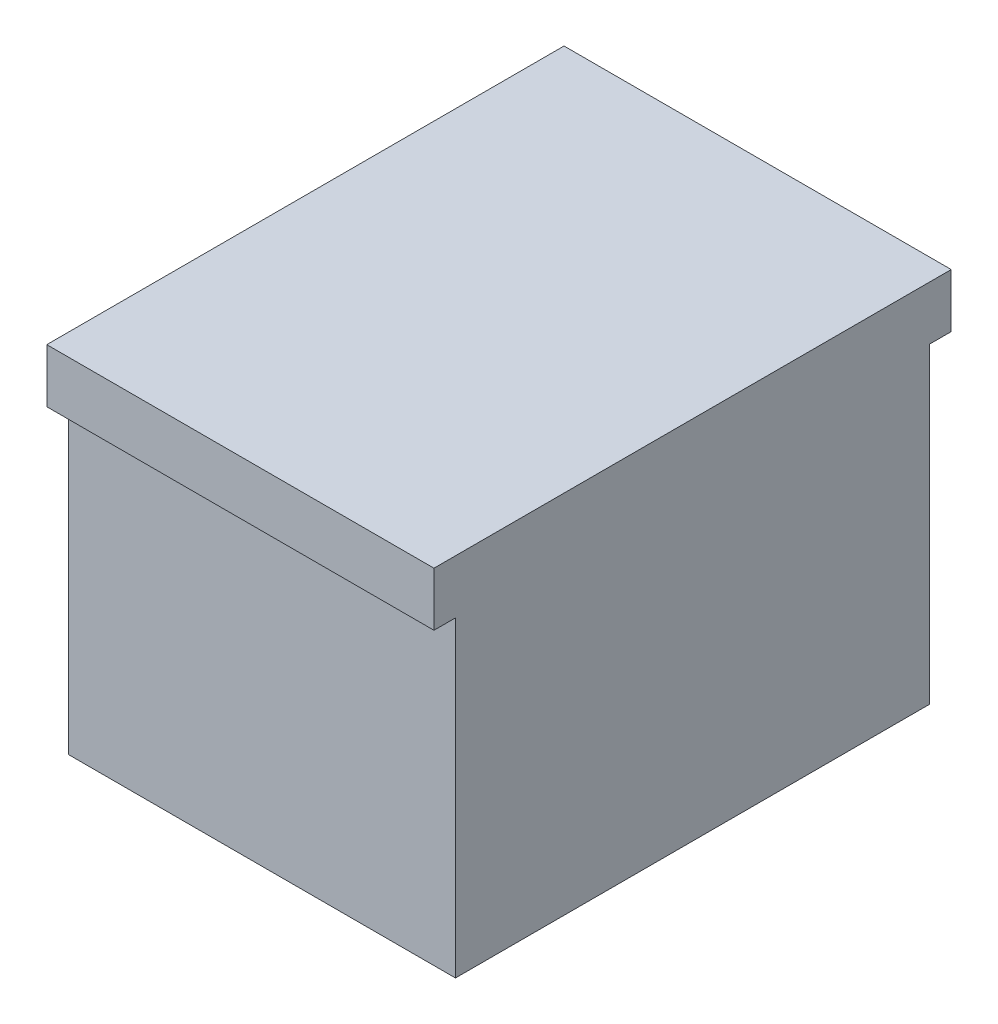
SolidWorks part; units mm, degrees
material "leadbattery"
ref_plane "Front" through (0, 0, 0) normal (0, 0, 1) x (1, 0, 0)
ref_plane "Top" through (0, 0, 0) normal (0, 1, 0) x (1, 0, 0)
ref_plane "Right" through (0, 0, 0) normal (1, 0, 0) x (0, 0, -1)
sketch "Sketch1" plane through (0, 0, 0) normal (0, 1, 0) x (1, 0, 0)
  line L1 (114.3, 140) -> (-114.3, 140)
  line L2 (114.3, 140) -> (114.3, -140)
  line L3 (114.3, -140) -> (-114.3, -140)
  line L4 (-114.3, 140) -> (-114.3, -140)
  line L5 (114.3, 140) -> (-114.3, -140) construction
  line L6 (114.3, -140) -> (-114.3, 140) construction
  point P0 (0, 0)
  dimension "D1" = 228.6
  dimension "D2" = 280
extrude "Boss-Extrude1" add sketch "Sketch1" along normal blind 215.9
hole_wizard "M5 Clearance Hole1" positions "Sketch2" profile "Sketch3" hole size "M5" standard "ANSI Metric"
sketch "Sketch2" plane through (0, 0, 0) normal (0, -1, 0) x (-1, 0, 0)
  line L0 (114.3, -140) -> (-114.3, -140) construction
  line L2 (-114.3, -140) -> (-114.3, 140) construction
  line L3 (57.6835, 70.566) -> (57.6835, -81.326)
  line L4 (57.6835, -81.326) -> (-76.2, -5.38)
  line L5 (-76.2, -5.38) -> (57.6835, 70.566)
  point P0 (-76.2, -5.38)
  point P19 (57.6835, 70.566)
  point P21 (57.6835, -81.326)
  dimension "D1" = 134.62
  dimension "D2" = 38.1
  dimension "D3" = 151.892
  dimension "D4" = 153.924
  dimension "D5" = 153.924
sketch "Sketch3" plane through (76.2, 0, 5.38) normal (1, 0, 0) x (0, 0, -1)
  line L0 (0, 0) -> (0, 41.6524)
  line L1 (0, 41.6524) -> (2.75, 40)
  line L2 (2.75, 40) -> (2.75, 0)
  line L5 (2.75, 0) -> (0, 0)
  line L10 (0, 41.6524) -> (-2.75, 40) construction
  line L11 (0, -6.35) -> (0, 107.95) construction
  dimension "Hole Dia." = 5.5
  dimension "Hole Depth" = 40
  dimension "Drill Angle" = 118
sketch "Sketch4" plane through (0, 0, 0) normal (0, -1, 0) x (1, 0, 0)
  circle A0 centre (-57.6835, -70.566) radius 7.3787
  circle A1 centre (-57.6835, -70.566) radius 2.75 construction
  circle A2 centre (-57.6835, -70.566) radius 2.75
  circle A3 centre (-57.6835, 81.326) radius 7.3787
  circle A4 centre (-57.6835, 81.326) radius 2.75 construction
  circle A5 centre (-57.6835, 81.326) radius 2.75
  dimension "D1" = 14.7574
extrude "Boss-Extrude2" add sketch "Sketch4" along normal blind 10.5918
sketch "Sketch5" plane through (0, 215.9, 0) normal (0, 1, 0) x (1, 0, 0)
  line L0 (-114.3, 140) -> (-114.3, -140) construction
  line L1 (114.3, -152.7) -> (-114.3, -152.7)
  line L2 (114.3, -152.7) -> (114.3, 152.7)
  line L3 (114.3, 152.7) -> (-114.3, 152.7)
  line L4 (-114.3, -152.7) -> (-114.3, 152.7)
  line L5 (114.3, -152.7) -> (-114.3, 152.7) construction
  line L6 (114.3, 152.7) -> (-114.3, -152.7) construction
  line L7 (114.3, 140) -> (-114.3, 140) construction
  point P0 (0, 0)
  dimension "D1" = 12.7
extrude "Boss-Extrude3" add sketch "Sketch5" against normal blind 31.75
ref_axis "Axis1" through (-57.6835, -10.5918, 81.326) along (0, 1, 0)
ref_axis "Axis2" through (-57.6835, -10.5918, -70.566) along (0, 1, 0)
ref_plane "Plane1" through (-57.6835, 0, 0) normal (-1, 0, 0) x (0, 0, 1)
